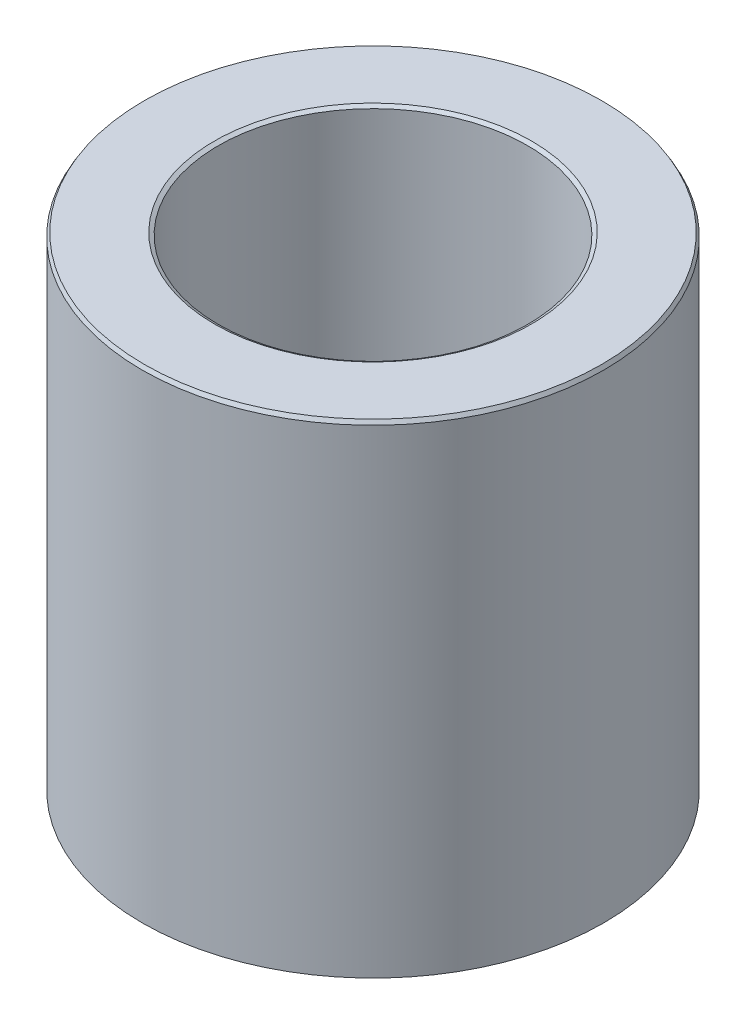
SolidWorks part; units mm, degrees
ref_plane "Front Plane" through (0, 0, 0) normal (0, 0, 1) x (1, 0, 0)
ref_plane "Top Plane" through (0, 0, 0) normal (0, 1, 0) x (1, 0, 0)
ref_plane "Right Plane" through (0, 0, 0) normal (1, 0, 0) x (0, 0, -1)
sketch "Sketch1" plane through (0, 0, 0) normal (0, 1, 0) x (1, 0, 0)
  circle A0 centre (0, 0) radius 27.5
  dimension "SLEEVE_OD" = 55
extrude "Boss-Extrude1" add sketch "Sketch1" along normal blind 57.7615
sketch "Sketch2" plane through (0, 0, 0) normal (0, 1, 0) x (1, 0, 0)
  circle A0 centre (0, 0) radius 18.4467
  dimension "BORE_D" = 36.8933
extrude "Cut-Extrude1" cut sketch "Sketch2" along normal through all
chamfer "Chamfer1" distance 0.4492 angle 30 4 edges at (0, 57.7615, 18.4467) (0, 0, 18.4467) (0, 0, 27.5) (0, 57.7615, 27.5) first distance on face at (0, 57.7615, 18.4467) first distance on face at (0, 0, 18.4467) first distance on face at (0, 57.7615, 27.5)
